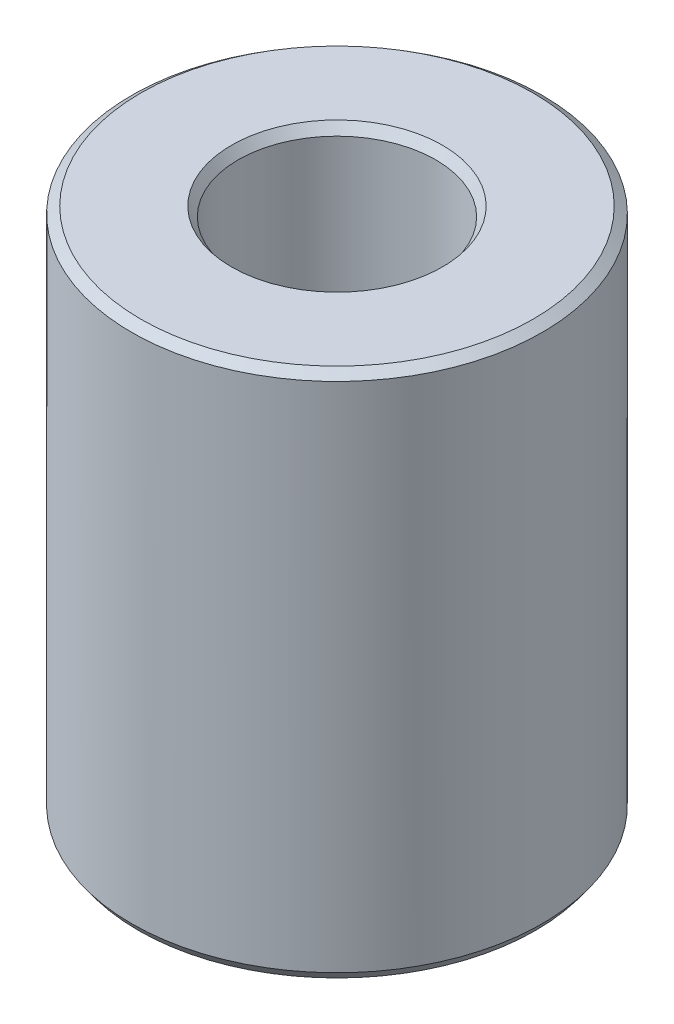
SolidWorks part; units mm, degrees
ref_plane "Front Plane" through (0, 0, 0) normal (0, 0, 1) x (1, 0, 0)
ref_plane "Top Plane" through (0, 0, 0) normal (0, 1, 0) x (1, 0, 0)
ref_plane "Right Plane" through (0, 0, 0) normal (1, 0, 0) x (0, 0, -1)
sketch "Sketch1" plane through (0, 0, 0) normal (0, 1, 0) x (1, 0, 0)
  circle A0 centre (0, 0) radius 10
  dimension "SLEEVE_OD" = 20
extrude "Boss-Extrude1" add sketch "Sketch1" along normal blind 25.719
sketch "Sketch2" plane through (0, 0, 0) normal (0, 1, 0) x (1, 0, 0)
  circle A0 centre (0, 0) radius 4.8103
  dimension "BORE_D" = 9.6206
extrude "Cut-Extrude1" cut sketch "Sketch2" along normal through all
chamfer "Chamfer1" distance 0.3278 angle 54.045 4 edges at (0, 25.719, 4.8103) (0, 0, 4.8103) (0, 0, 10) (0, 25.719, 10) first distance on face at (0, 25.719, 4.8103) first distance on face at (0, 0, 4.8103) first distance on face at (0, 25.719, 10)
